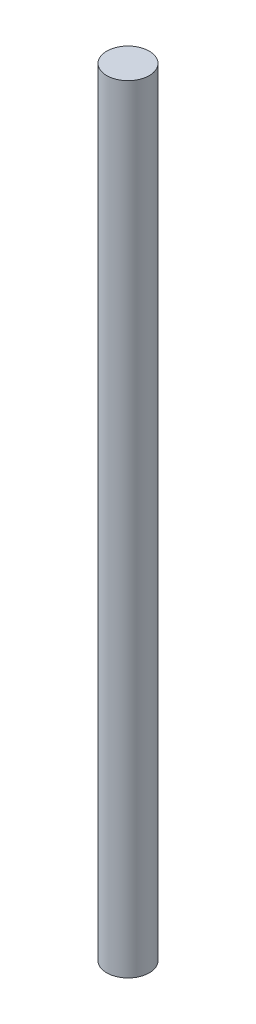
SolidWorks part; units mm, degrees
ref_plane "前视基准面" through (0, 0, 0) normal (0, 0, 1) x (1, 0, 0)
ref_plane "上视基准面" through (0, 0, 0) normal (0, 1, 0) x (1, 0, 0)
ref_plane "右视基准面" through (0, 0, 0) normal (1, 0, 0) x (0, 0, -1)
other "Configuration Table"
sketch "草图1" plane through (0, 0, 0) normal (0, 1, 0) x (1, 0, 0)
  circle A0 centre (0, 0) radius 4
  dimension "D1" = 8
extrude "凸台-拉伸1" add sketch "草图1" along normal blind 125
sketch "草图2" plane through (0, 0, 0) normal (0, -1, 0) x (1, 0, 0)
  circle A1 centre (0, 0) radius 4
  circle A2 centre (0, 0) radius 4
  dimension "D1" = 0
extrude "凸台-拉伸2" add sketch "草图2" along normal up to surface (21.39 mm away) up to face at (0, 125, 4)
